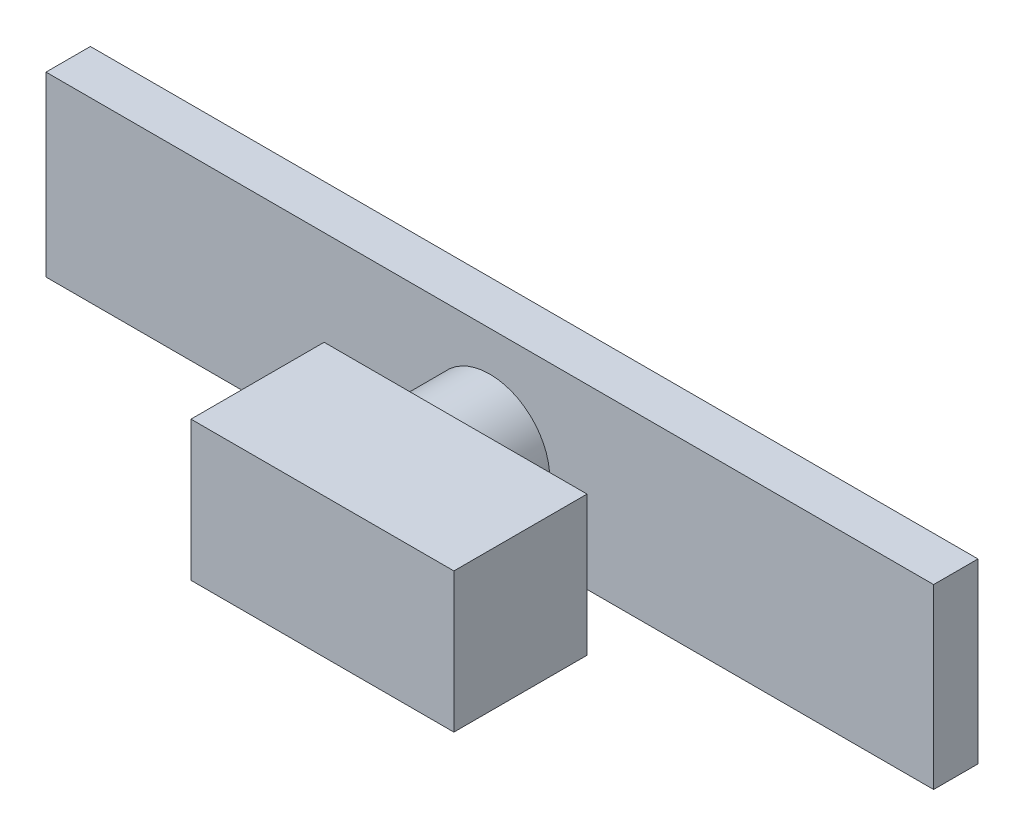
SolidWorks part; units mm, degrees
ref_plane "Front Plane" through (0, 0, 0) normal (0, 0, 1) x (1, 0, 0)
ref_plane "Top Plane" through (0, 0, 0) normal (0, 1, 0) x (1, 0, 0)
ref_plane "Right Plane" through (0, 0, 0) normal (1, 0, 0) x (0, 0, -1)
sketch "Sketch2" plane through (0, 0, 0) normal (0, 0, 1) x (1, 0, 0)
  line L1 (-47.8692, 21.2481) -> (206.1308, 21.2481)
  line L2 (-47.8692, 21.2481) -> (-47.8692, 8.5481)
  line L3 (-47.8692, 8.5481) -> (206.1308, 8.5481)
  line L4 (206.1308, 21.2481) -> (206.1308, 8.5481)
  dimension "D1" = 12.7
  dimension "D2" = 254
extrude "Boss-Extrude1" add sketch "Sketch2" along normal blind 50.8
sketch "Sketch3" plane through (0, 21.2481, 0) normal (0, 1, 0) x (1, 0, 0)
  circle A0 centre (79.1308, -28.4831) radius 17.1408
extrude "Boss-Extrude2" add sketch "Sketch3" along normal blind 19.05
sketch "Sketch4" plane through (0, 40.2981, 0) normal (0, 1, 0) x (1, 0, 0)
  line L1 (50.7675, -8.111) -> (126.0034, -8.111)
  line L2 (50.7675, -8.111) -> (50.7675, -48.0661)
  line L3 (50.7675, -48.0661) -> (126.0034, -48.0661)
  line L4 (126.0034, -8.111) -> (126.0034, -48.0661)
extrude "Boss-Extrude3" add sketch "Sketch4" along normal blind 38.1
scale "Scale2" scale about centroid uniform scaling yes scale factor 0.06
move or copy body "rotate" bodies to move or copy 105 copy no rotation origin (0, 33.6669, 26.5501) rotation axis (1, 0, 0) rotation angle 90
scale "Scale5" scale about centroid uniform scaling yes scale factor 0.25
move or copy body "-4 x" bodies to move or copy 111 copy no translate (-101.6, 0, 0)
move or copy body "-2 y" bodies to move or copy 117 copy no translate (0, -50.8, 0)
scale "Scale6" bodies to scale 121 scale about centroid uniform scaling yes scale factor 0.25
move or copy body "-2.1z" bodies to move or copy 122 copy no translate (0, 0, -38.1)
